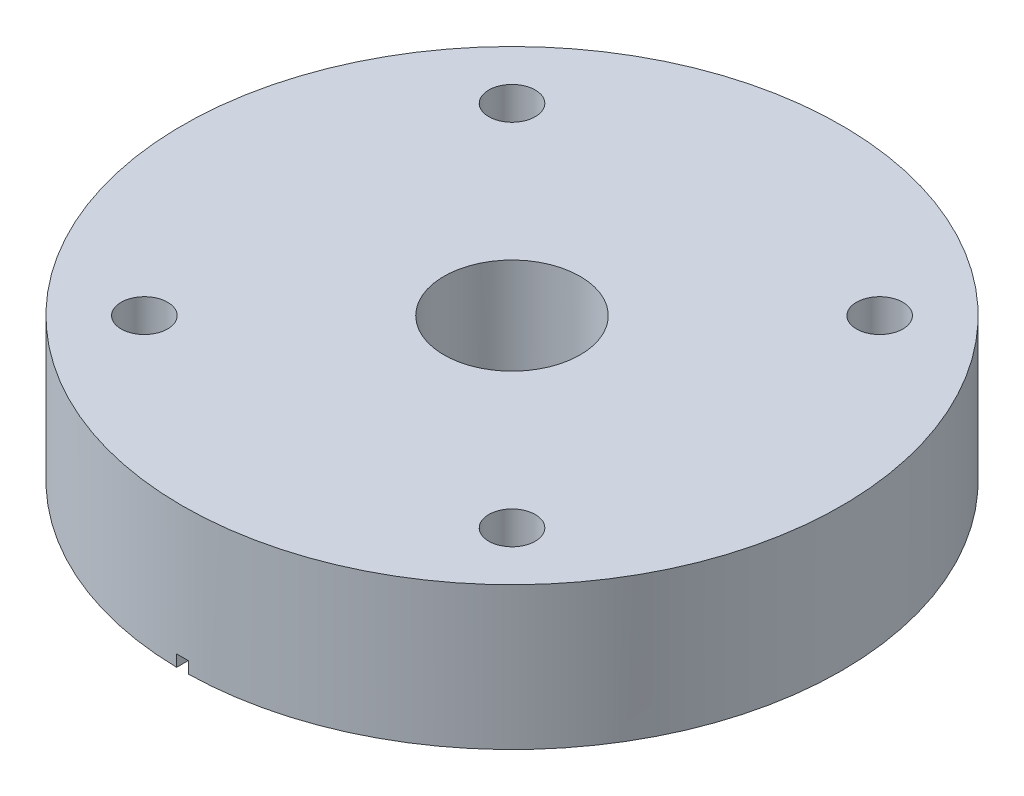
SolidWorks part; units mm, degrees
material "1060 Alloy"
ref_plane "Front" through (0, 0, 0) normal (0, 0, 1) x (1, 0, 0)
ref_plane "Top" through (0, 0, 0) normal (0, 1, 0) x (1, 0, 0)
ref_plane "Right" through (0, 0, 0) normal (1, 0, 0) x (0, 0, -1)
sketch "Sketch1" plane through (0, 0, 0) normal (0, 1, 0) x (1, 0, 0)
  line L0 (0, 0) -> (0, 44.45) construction
  circle A0 centre (-31.4309, 31.4309) radius 3.9688
  circle A1 centre (31.4309, 31.4309) radius 3.9687
  circle A2 centre (31.4309, -31.4309) radius 3.9687
  circle A3 centre (-31.4309, -31.4309) radius 3.9688
  circle A4 centre (0, 0) radius 10.1459
  arc A5 (-24.1039, 40.8157) -> (-40.8157, 24.1039) centre (-31.4309, 31.4309) ccw construction
  arc A6 (40.8157, 24.1039) -> (24.1039, 40.8157) centre (31.4309, 31.4309) ccw construction
  arc A7 (24.1039, -40.8157) -> (40.8157, -24.1039) centre (31.4309, -31.4309) ccw construction
  arc A8 (-40.8157, -24.1039) -> (-24.1039, -40.8157) centre (-31.4309, -31.4309) ccw construction
  arc A9 (-40.2313, 18.9009) -> (-40.2313, -18.9009) centre (0, 0) ccw construction
  arc A10 (-18.9009, -40.2313) -> (18.9009, -40.2313) centre (0, 0) ccw construction
  arc A11 (40.2313, -18.9009) -> (40.2313, 18.9009) centre (0, 0) ccw construction
  arc A12 (-18.9009, 40.2313) -> (-24.1039, 40.8157) centre (-21.027, 44.7568) cw construction
  arc A13 (18.9009, 40.2313) -> (-18.9009, 40.2313) centre (0, 0) ccw construction
  arc A14 (24.1039, 40.8157) -> (18.9009, 40.2313) centre (21.027, 44.7568) cw construction
  arc A15 (40.8157, 24.1039) -> (40.2313, 18.9009) centre (44.7568, 21.027) ccw construction
  arc A16 (40.2313, -18.9009) -> (40.8157, -24.1039) centre (44.7568, -21.027) ccw construction
  arc A17 (24.1039, -40.8157) -> (18.9009, -40.2313) centre (21.027, -44.7568) ccw construction
  arc A18 (-18.9009, -40.2313) -> (-24.1039, -40.8157) centre (-21.027, -44.7568) ccw construction
  arc A19 (-40.2313, -18.9009) -> (-40.8157, -24.1039) centre (-44.7568, -21.027) cw construction
  arc A20 (-40.2313, 18.9009) -> (-40.8157, 24.1039) centre (-44.7568, 21.027) ccw construction
  circle A21 centre (0, 0) radius 56.3562
  point P0 (0, 0)
  point P17 (0, 0)
  point P27 (0, 0)
  point P40 (0, 0)
  point P42 (0, 0)
  point P43 (0, 0)
  point P44 (0, 0)
  point P45 (0, 44.45)
  dimension "D5" = 7.9375
  dimension "D6" = 20.2918
  dimension "D1" = 5
  dimension "D2" = 11.9062
  dimension "D3" = 44.45
  dimension "D4" = 4
  dimension "D8" = 4
extrude "body and main holes" add sketch "Sketch1" along normal blind 24.4122
sketch "Sketch3" plane through (0, 24.4122, 0) normal (0, -1, 0) x (1, 0, 0)
  circle A0 centre (0, 0) radius 11.6459
  dimension "D1" = 23.2918
extrude "seal bore" cut sketch "Sketch3" along normal blind 22.4122
sketch "Sketch4" plane through (0, 0, 0) normal (0, -1, 0) x (1, 0, 0)
  line L0 (0, 0) -> (0, 44.45) construction
  line L2 (-1, 56.3563) -> (1, 56.3563)
  line L3 (-1, 56.3563) -> (-1, -56.3562)
  line L4 (-1, -56.3562) -> (1, -56.3562)
  line L5 (1, 56.3563) -> (1, -56.3562)
  line L6 (-1, 56.3563) -> (1, -56.3562) construction
  line L7 (-1, -56.3562) -> (1, 56.3563) construction
  circle A2 centre (0, 0) radius 56.3562 construction
  point P6 (0, 0)
  point P14 (0, 0)
  point P15 (0, 0)
  dimension "D1" = 2
extrude "vent slot" cut sketch "Sketch4" against normal blind 2
equation "\"D3@Sketch1\"=\"square plate bolt pattern diameter\"/2"
equation "\"D1@body and main holes\" = \"lower seal plate thickness\""
equation "\"D1@Sketch3\" = \"lower seal OD\""
equation "\"D1@seal bore\" = \"lower seal bore\""
equation "\"D5@Sketch1\"=\"m8 clearance\""
equation "\"D6@Sketch1\" = \"lower seal plate lip ID\""
equation "\"square plate bolt pattern diameter\"= 3.5in"
equation "\"square plate bolt bore\" = \"m8 clearance\""
equation "\"square plate bolt head diameter\" = 13.5mm"
equation "\"motor OD\" = 64mm"
equation "\"m6 clearance\" = 0.234375in 'this is 15/64 bit = 5.95mm, could use 6mm bit, B bit for 6.04mm or 1/4 bit for 6.35mm"
equation "\"m6 tap\" = 5mm   '5mm is appropriate, could use 13/64 or #5,6,7"
equation "\"m6 head bore diameter\" = 11mm  "
equation "\"m6 head bore depth\" = 7mm 'actual is 6mm"
equation "\"m8 clearance\" = 0.3125in 'this is 5/16in for 7.93mm, could use 8mm, O,P, or 21/64"
equation "\"m8 tap\" = 0.265625in  'this is 17/64 for 6.746875mm"
equation "\"m8 head bore diameter\" = 14mm"
equation "\"m8 head bore depth\" = 9mm 'actual is 8mm"
equation "\"lower seal OD\" = .917in  'this is https://www.mcmaster.com/#9281k121/=174001b"
equation "\"lower seal ID\"= .375in"
equation "\"lower seal depth\" = .625in + .218in"
equation "\"lower seal bore\" = \"lower seal depth\" + 1mm"
equation "\"impeller upper clearance\"= .5mm"
equation "\"impeller bottom clearance\"= .5mm"
equation "\"impeller dowel diameter\" = 2mm"
equation "\"impeller shaft bore depth\" = 12mm"
equation "\"impeller shaft bore\" = 8mm"
equation "\"impeller dowel length\" = 2mm*2 + \"impeller shaft bore\""
equation "\"square plate bolt head depth\" = 8mm"
equation "\"lower seal plate lip depth\" = 2mm"
equation "\"lower seal plate lip ID\" = \"lower seal OD\" - 3mm"
equation "\"lower seal plate thickness\" = \"lower seal plate lip depth\" + \"lower seal bore\""
equation "\"shaft coupler section diameter\" = 8mm"
equation "\"shaft bearing stop length\" = 3mm"
equation "\"shaft lower seal section diameter\" = \"lower seal ID\""
equation "\"shaft lower seal section length\" = \"lower seal plate thickness\" + 1mm"
equation "\"shaft impeller section diameter\" = \"impeller shaft bore\""
equation "\"upper seal plate pressure tap diameter\" = .328125in  'this is 21/64 drill for a 1/8 ANPT tap"
equation "\"motor mount post radius\"= ( 3 * \"square plate bolt bore\" ) / 2"
